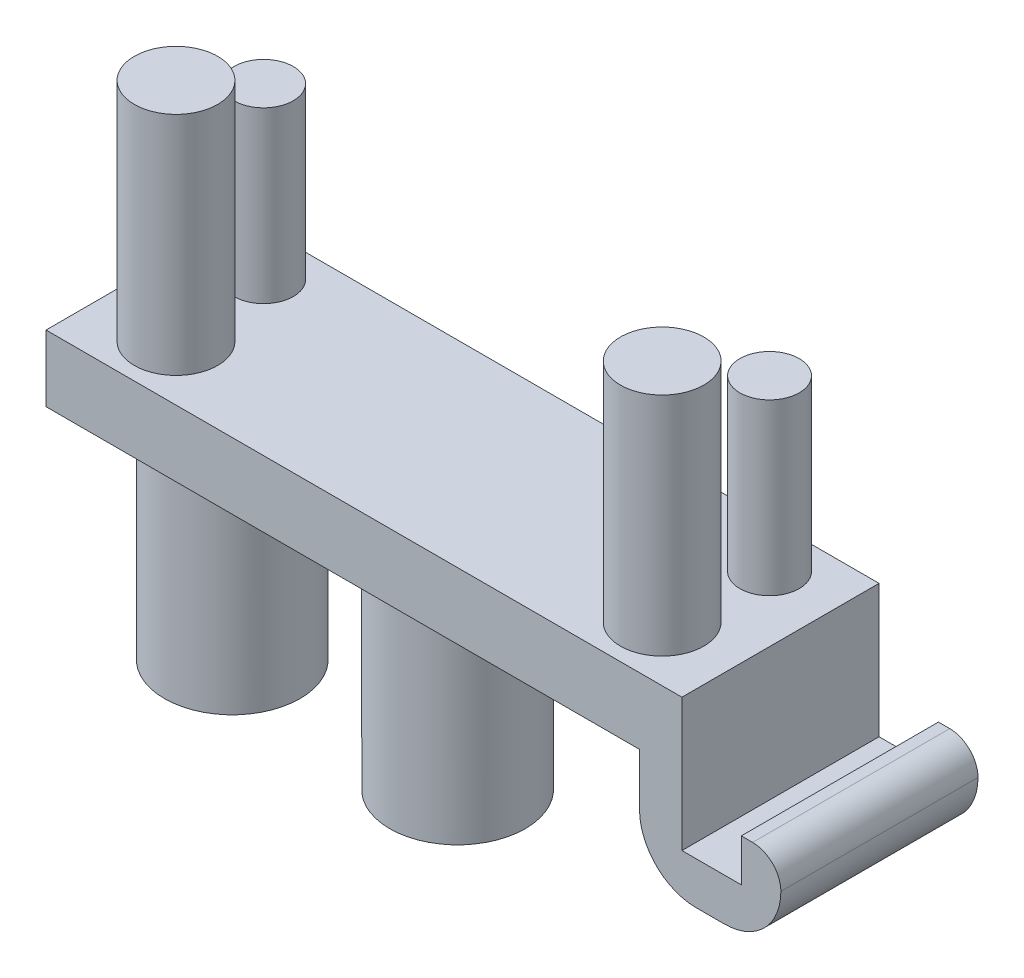
SolidWorks part; units mm, degrees
ref_plane "Front Plane" through (0, 0, 0) normal (0, 0, 1) x (1, 0, 0)
ref_plane "Top Plane" through (0, 0, 0) normal (0, 1, 0) x (1, 0, 0)
ref_plane "Right Plane" through (0, 0, 0) normal (1, 0, 0) x (0, 0, -1)
sketch "Sketch1" plane through (0, 0, 0) normal (0, 1, 0) x (1, 0, 0)
  line L1 (-27.9651, -5.433) -> (-5.4651, -5.433)
  line L2 (-27.9651, -5.433) -> (-27.9651, -12.408)
  line L3 (-27.9651, -12.408) -> (-5.4651, -12.408)
  line L4 (-5.4651, -5.433) -> (-5.4651, -12.408)
  dimension "D1" = 6.975
  dimension "D2" = 22.5
extrude "Boss-Extrude1" add sketch "Sketch1" along normal blind 2.35
sketch "Sketch2" plane through (0, 2.35, 0) normal (0, 1, 0) x (1, 0, 0)
  line L0 (-27.9651, -5.433) -> (-27.9651, -12.408) construction
  line L2 (-27.9651, -12.408) -> (-5.4651, -12.408) construction
  circle A0 centre (-25.3151, -10.458) radius 1.475
  circle A1 centre (-8.1151, -10.458) radius 1.475
  dimension "D1" = 2.95
  dimension "D2" = 2.95
  dimension "D3" = 2.65
  dimension "D4" = 17.2
  dimension "D5" = 1.95
  dimension "D6" = 1.95
extrude "Boss-Extrude2" add sketch "Sketch2" along normal blind 8
sketch "Sketch3" plane through (0, 0, 0) normal (0, -1, 0) x (-1, 0, 0)
  line L0 (5.4651, -5.433) -> (27.9651, -5.433) construction
  line L1 (5.4651, -5.433) -> (6.9651, -5.433)
  line L2 (5.4651, -5.433) -> (5.4651, -12.408)
  line L3 (5.4651, -12.408) -> (6.9651, -12.408)
  line L4 (6.9651, -5.433) -> (6.9651, -12.408)
  line L5 (27.9651, -12.408) -> (5.4651, -12.408) construction
  dimension "D1" = 1.5
extrude "Boss-Extrude3" add sketch "Sketch3" along normal blind 3.85
sketch "Sketch4" plane through (-5.4651, 0, 0) normal (1, 0, 0) x (0, 0, -1)
  line L0 (-12.408, 2.35) -> (-12.408, -3.85) construction
  line L1 (-5.433, -3.85) -> (-12.408, -3.85)
  line L2 (-5.433, -3.85) -> (-5.433, -0.85)
  line L3 (-5.433, -0.85) -> (-12.408, -0.85)
  line L4 (-12.408, -3.85) -> (-12.408, -0.85)
  dimension "D1" = 3
extrude "Boss-Extrude4" add sketch "Sketch4" along normal blind 3.5
sketch "Sketch5" plane through (0, -0.85, 0) normal (0, 1, 0) x (1, 0, 0)
  line L0 (-1.9651, -12.408) -> (-5.4651, -12.408) construction
  line L1 (-5.4651, -5.433) -> (-3.3651, -5.433)
  line L2 (-5.4651, -5.433) -> (-5.4651, -12.408)
  line L3 (-5.4651, -12.408) -> (-3.3651, -12.408)
  line L4 (-3.3651, -5.433) -> (-3.3651, -12.408)
  line L5 (-1.9651, -5.433) -> (-1.9651, -12.408) construction
  point P7 (-4.6375, -11.1978)
  dimension "D1" = 1.4
extrude "Cut-Extrude1" cut sketch "Sketch5" against normal blind 1.5
sketch "Sketch6" plane through (0, 2.35, 0) normal (0, 1, 0) x (1, 0, 0)
  circle A0 centre (-7.7651, -7.008) radius 1.05
  circle A1 centre (-25.6651, -7.008) radius 1.05
  circle A2 centre (-25.3151, -10.458) radius 1.475 construction
  circle A3 centre (-8.1151, -10.458) radius 1.475 construction
  dimension "D1" = 2.1
  dimension "D2" = 2.1
  dimension "D3" = 3.45
  dimension "D4" = 0.35
  dimension "D5" = 0.35
  dimension "D6" = 3.45
extrude "Boss-Extrude5" add sketch "Sketch6" along normal blind 6
sketch "Sketch7" plane through (0, 0, 0) normal (0, -1, 0) x (-1, 0, 0)
  line L0 (27.9651, -5.433) -> (27.9651, -12.408) construction
  circle A0 centre (16.7151, -9.098) radius 2.4
  circle A1 centre (8.1151, -10.458) radius 1.475 construction
  circle A2 centre (24.6851, -9.098) radius 2.4
  dimension "D1" = 4.8
  dimension "D2" = 11.25
  dimension "D3" = 1.36
  dimension "D4" = 4.8
  dimension "D5" = 0
  dimension "D6" = 7.97
extrude "Boss-Extrude9" add sketch "Sketch7" along normal blind 7.76
fillet "Fillet1" radius 2 1 edges at (-6.9651, -3.85, 8.9205) type face fillet first side face at (-6.9651, -1.925, 8.9205) second side face at (-4.4651, -3.85, 8.9205)
fillet "Fillet2" radius 2 1 edges at (-1.9651, -3.85, 8.9205) type face fillet first side face at (-3.4651, -3.85, 8.9205) second side face at (-1.9651, -2.35, 8.9205)
fillet "Fillet3" radius 1 1 edges at (-1.9651, -0.85, 8.9205) type face fillet first side face at (-1.9651, -1.35, 8.9205) second side face at (-2.6651, -0.85, 8.9205)
